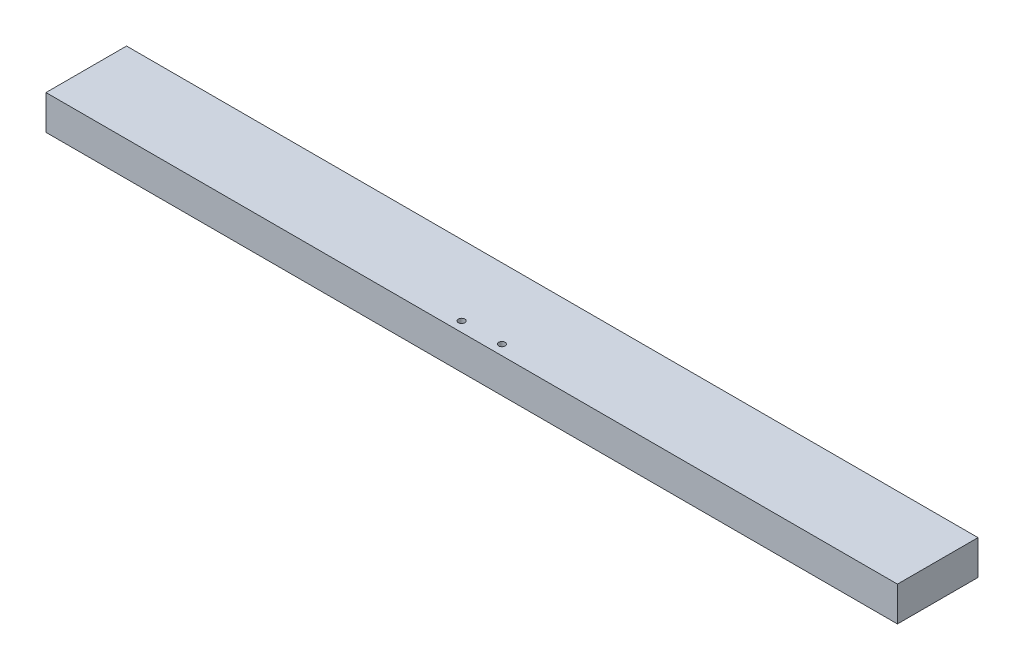
SolidWorks part; units mm, degrees
ref_plane "Front Plane" through (0, 0, 0) normal (0, 0, 1) x (1, 0, 0)
ref_plane "Top Plane" through (0, 0, 0) normal (0, 1, 0) x (1, 0, 0)
ref_plane "Right Plane" through (0, 0, 0) normal (1, 0, 0) x (0, 0, -1)
sketch "Sketch1" plane through (0, 0, 0) normal (0, 0, 1) x (1, 0, 0)
  line L1 (-469.8492, -19.05) -> (469.8492, -19.05)
  line L2 (-469.8492, -19.05) -> (-469.8492, 19.05)
  line L3 (-469.8492, 19.05) -> (469.8492, 19.05)
  line L4 (469.8492, -19.05) -> (469.8492, 19.05)
  line L5 (-469.8492, -19.05) -> (469.8492, 19.05) construction
  line L6 (-469.8492, 19.05) -> (469.8492, -19.05) construction
  point P0 (0, 0)
  dimension "D1" = 38.1
  dimension "D2" = 939.6984
extrude "Boss-Extrude1" add sketch "Sketch1" along normal blind 88.9
sketch "Sketch2" plane through (0, 19.05, 0) normal (0, 1, 0) x (1, 0, 0)
  line L0 (0, 0) -> (0, -88.9) construction
  line L1 (469.8492, 0) -> (-469.8492, 0) construction
  line L2 (469.8492, -88.9) -> (-469.8492, -88.9) construction
  line L4 (-28.575, -85.725) -> (28.575, -85.725)
  line L5 (-28.575, -85.725) -> (-28.575, -69.85)
  line L6 (-28.575, -69.85) -> (28.575, -69.85)
  line L7 (28.575, -85.725) -> (28.575, -69.85)
  line L8 (-28.575, -85.725) -> (28.575, -69.85) construction
  line L9 (-28.575, -69.85) -> (28.575, -85.725) construction
  circle A0 centre (-22.225, -77.7875) radius 3.5719
  circle A1 centre (22.225, -77.7875) radius 3.5719
  point P6 (0, -77.7875)
  dimension "D5" = 7.1437
  dimension "D6" = 7.1437
  dimension "D1" = 15.875
  dimension "D2" = 57.15
  dimension "D3" = 22.225
  dimension "D4" = 22.225
  dimension "D7" = 7.9375
  dimension "D8" = 7.9375
  dimension "D9" = 69.85
extrude "Cut-Extrude1" cut sketch "Sketch2" against normal through all contours A1 | A0 region at (22.225, 19.05, 77.7875)
